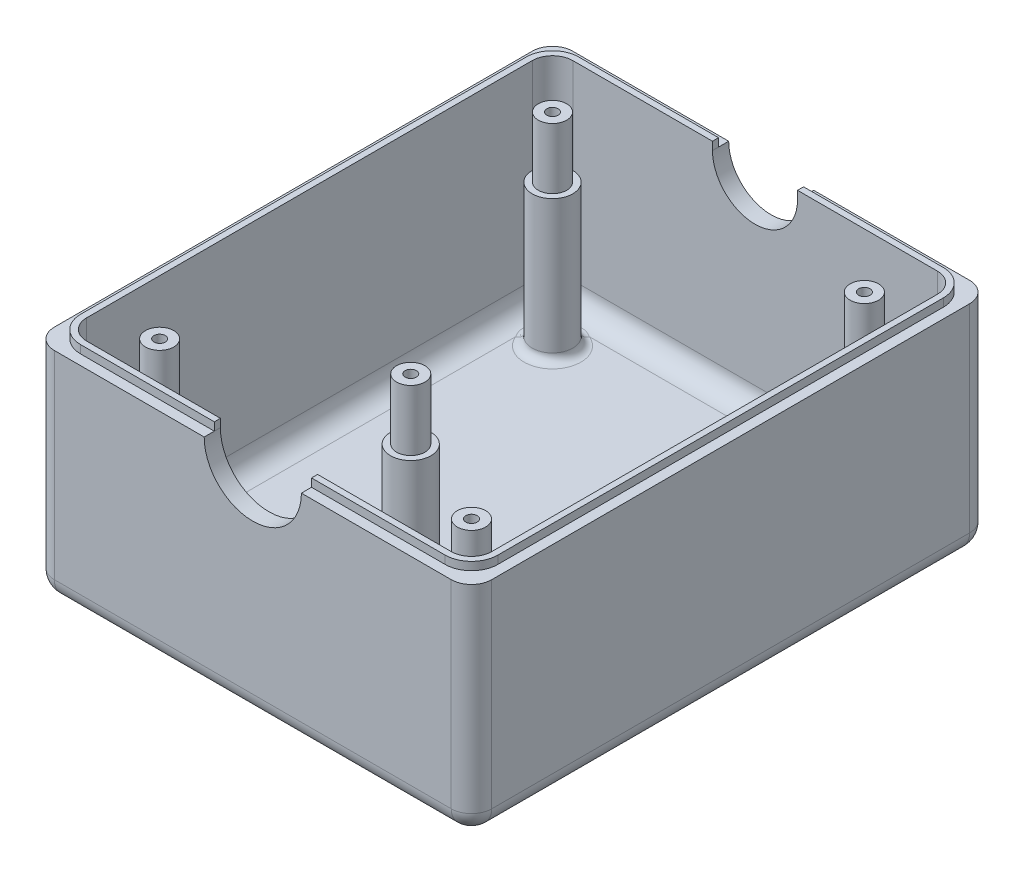
SolidWorks part; units mm, degrees
ref_plane "Front Plane" through (0, 0, 0) normal (0, 0, 1) x (1, 0, 0)
ref_plane "Top Plane" through (0, 0, 0) normal (0, 1, 0) x (1, 0, 0)
ref_plane "Right Plane" through (0, 0, 0) normal (1, 0, 0) x (0, 0, -1)
sketch "Sketch2" plane through (0, 0, 0) normal (0, 0, 1) x (1, 0, 0)
  line L0 (-50, 50) -> (-50, 0)
  line L1 (-50, 0) -> (50, 0)
  line L2 (50, 0) -> (50, 50)
  point P4 (0, 0)
  dimension "D1" = 50
  dimension "D2" = 100
  dimension "D3" = 50
extrude "Extrude-Thin2" add sketch "Sketch2" along normal blind 120 thin
sketch "Sketch5" plane through (0, 50, 0) normal (0, 1, 0) x (1, 0, 0)
  line L1 (-54, -120) -> (-50, -120) construction
  line L2 (-50, -120) -> (50, -120) construction
  line L3 (50, -120) -> (54, -120) construction
  line L4 (50, -120) -> (54, -120)
  line L5 (-50, -120) -> (50, -120)
  line L6 (-54, -120) -> (-50, -120)
extrude "Extrude-Thin3" add sketch "Sketch5" against normal up to surface (54 mm away) thin
sketch "Sketch7" plane through (0, 50, 0) normal (0, 1, 0) x (1, 0, 0)
  line L0 (50, 0) -> (54, 0) construction
  line L1 (-50, 0) -> (50, 0) construction
  line L2 (-54, 0) -> (-50, 0) construction
  line L3 (50, 0) -> (54, 0)
  line L4 (-50, 0) -> (50, 0)
  line L5 (-54, 0) -> (-50, 0)
extrude "Extrude-Thin4" add sketch "Sketch7" against normal up to surface (54 mm away) thin thin type one direction reverse wall 4
fillet "Fillet1" radius 5 7 edges at (54, -4, 60) (-54, -4, 60) (-54, 23, 124) (0, -4, 124) (54, 23, -4) (0, -4, -4) (-54, 23, -4)
fillet "Fillet2" radius 5 2 edges at (54, 25.5, 124) (52.5355, -2.5355, 122.5355)
fillet "Fillet3" radius 5 3 edges at (50, 0, 60) (0, 0, 0) (50, 25, 0)
fillet "Fillet4" radius 5 3 edges at (-50, 1.4645, 1.4645) (-50, 0, 62.5) (-50, 27.5, 0)
fillet "Fillet5" radius 5 5 edges at (50, 27.5, 120) (48.5355, 1.4645, 120) (0, 0, 120) (-48.5355, 1.4645, 120) (-50, 27.5, 120)
sketch "Sketch8" plane through (0, 0, 0) normal (0, 1, 0) x (1, 0, 0)
  line L0 (45, -5) -> (-45, -5) construction
  line L1 (-39.25, -15.7287) -> (39.25, -15.7287)
  line L2 (-39.25, -15.7287) -> (-39.25, -78.2287)
  line L3 (-39.25, -78.2287) -> (39.25, -78.2287)
  line L4 (39.25, -15.7287) -> (39.25, -78.2287)
  line L5 (45, -115) -> (45, -5) construction
  line L6 (0, 0) -> (0, -127.3693) construction
  line L7 (-45, -115) -> (45, -115) construction
  circle A0 centre (38.5, -11.5) radius 5
  circle A1 centre (-38.5, -11.5) radius 5
  circle A2 centre (-38.5, -108.5) radius 5
  circle A3 centre (38.5, -108.5) radius 5
  circle A4 centre (0, -85) radius 5
  point P4 (0, -15.7287)
  dimension "D7" = 10
  dimension "D8" = 10
  dimension "D9" = 10
  dimension "D1" = 78.5
  dimension "D2" = 62.5
  dimension "D3" = 6.5
  dimension "D4" = 6.5
  dimension "D5" = 6.5
  dimension "D6" = 30
extrude "Boss-Extrude1" add sketch "Sketch8" along normal blind 35 contours A1 | A0 | A4 | A2 | A3
sketch "Sketch10" plane through (0, 35, 0) normal (0, 1, 0) x (1, 0, 0)
  line L0 (0, 0) -> (0, -129.2583) construction
  circle A1 centre (38.5, -11.5) radius 5
  circle A2 centre (38.5, -11.5) radius 5
  circle A3 centre (38.5, -11.5) radius 3.5
  circle A4 centre (-38.5, -11.5) radius 3.5
  circle A5 centre (0, -85) radius 5 construction
  circle A6 centre (0, -85) radius 5
  circle A7 centre (0, -85) radius 3.5
  circle A8 centre (-38.5, -108.5) radius 5 construction
  circle A9 centre (-38.5, -108.5) radius 5
  circle A10 centre (-38.5, -108.5) radius 3.5
  circle A11 centre (38.5, -108.5) radius 3.5
  dimension "D2" = 7
  dimension "D3" = 7
  dimension "D4" = 7
  dimension "D1" = 0
extrude "Boss-Extrude2" add sketch "Sketch10" along normal up to surface (15 mm away) contours A3 | A4 | A7 | A11 | A10
sketch "Sketch11" plane through (0, 50, 0) normal (0, 1, 0) x (1, 0, 0)
  line L0 (0, 0) -> (0, -120) construction
  line L1 (45, -120) -> (-45, -120) construction
  circle A0 centre (-38.5, -11.5) radius 1.4
  circle A1 centre (-38.5, -11.5) radius 3.5
  circle A2 centre (-38.5, -11.5) radius 3.5
  circle A3 centre (38.5, -11.5) radius 1.4
  circle A4 centre (-38.5, -108.5) radius 1.4
  circle A5 centre (-38.5, -108.5) radius 3.5
  circle A6 centre (-38.5, -108.5) radius 3.5
  circle A7 centre (38.5, -108.5) radius 1.4
  circle A8 centre (0, -85) radius 1.4
  circle A9 centre (0, -85) radius 3.5
  circle A10 centre (0, -85) radius 3.5
  dimension "D2" = 2.8
  dimension "D4" = 2.8
  dimension "D6" = 2.8
  dimension "D1" = 0
  dimension "D3" = 0
  dimension "D5" = 0
extrude "Cut-Extrude1" cut sketch "Sketch11" against normal blind 28 contours A4 | A3 | A0 | A7 | A8
sketch "Sketch38" plane through (0, 0, 124) normal (0, 0, 1) x (1, 0, 0)
  line L0 (-49, 50) -> (49, 50) construction
  circle A0 centre (0, 50) radius 12
extrude "Cut-Extrude8" cut sketch "Sketch38" against normal blind 30
fillet "Fillet13" radius 2 1 edges at (-43.5, 0, 108.5)
sketch "Sketch40" plane through (0, 0, 0) normal (0, 1, 0) x (1, 0, 0)
  circle A0 centre (-38.5, -11.5) radius 3.75
  dimension "D1" = 7.5
extrude "Cut-Extrude9" cut sketch "Sketch40" against normal blind 32 and the other way blind 32
sketch "Sketch41" plane through (0, 0, 0) normal (0, 1, 0) x (1, 0, 0)
  circle A0 centre (38.5, -11.5) radius 3.75
  circle A1 centre (0, -85) radius 3.75
  circle A2 centre (-38.5, -108.5) radius 3.75
  circle A3 centre (38.5, -108.5) radius 3.75
  dimension "D1" = 7.5
  dimension "D2" = 7.5
  dimension "D3" = 7.5
  dimension "D4" = 7.5
extrude "Cut-Extrude10" cut sketch "Sketch41" along normal blind 32 and the other way blind 32
sketch "Sketch44" plane through (0, 50, 0) normal (0, 1, 0) x (1, 0, 0)
  line L0 (50, -5) -> (50, -115)
extrude "Extrude-Thin8" add sketch "Sketch44" along normal blind 2 thin thin type one direction reverse wall 1.5
sketch "Sketch50" plane through (0, 50, 0) normal (0, 1, 0) x (1, 0, 0)
  line L0 (-50, -5) -> (-50, -115)
extrude "Extrude-Thin12" add sketch "Sketch50" along normal blind 2 thin
sketch "Sketch51" plane through (0, 50, 0) normal (0, 1, 0) x (1, 0, 0)
  line L0 (-45, 0) -> (45, 0) construction
  line L1 (-45, 0) -> (45, 0) construction
  line L2 (-45, 0) -> (45, 0)
  line L3 (50, -5) -> (50, -115) construction
  line L4 (50, -5) -> (50, -115) construction
  arc A0 (-50, -5) -> (-45, 0) centre (-45, -5) cw
  arc A1 (45, 0) -> (50, -5) centre (45, -5) cw
extrude "Extrude-Thin13" add sketch "Sketch51" along normal blind 2 thin thin type one direction reverse wall 1.5
sketch "Sketch52" plane through (0, 50, 0) normal (0, 1, 0) x (1, 0, 0)
  line L0 (-45, -120) -> (-12, -120)
  arc A0 (-50, -115) -> (-45, -120) centre (-45, -115) ccw
  arc A1 (-50, -115) -> (-45, -120) centre (-45, -115) ccw construction
  arc A2 (-50, -115) -> (-45, -120) centre (-45, -115) ccw construction
extrude "Extrude-Thin14" add sketch "Sketch52" along normal blind 2 thin
sketch "Sketch53" plane through (0, 50, 0) normal (0, 1, 0) x (1, 0, 0)
  line L0 (45, -120) -> (12, -120)
  arc A0 (50, -115) -> (45, -120) centre (45, -115) cw
extrude "Extrude-Thin15" add sketch "Sketch53" along normal blind 2 thin thin type one direction reverse wall 1.5
sketch "Sketch60" plane through (0, 0, -4) normal (0, 0, -1) x (-1, 0, 0)
  line L0 (49, 50) -> (-49, 50) construction
  circle A0 centre (0, 50) radius 10.5
  dimension "D1" = 21
extrude "Cut-Extrude13" cut sketch "Sketch60" against normal blind 10
sketch "Sketch61" plane through (0, 0, -4) normal (0, 0, -1) x (-1, 0, 0)
  line L1 (-10.5, 50) -> (10.5, 50)
  line L2 (-10.5, 50) -> (-10.5, 52.7523)
  line L3 (-10.5, 52.7523) -> (10.5, 52.7523)
  line L4 (10.5, 50) -> (10.5, 52.7523)
extrude "Cut-Extrude14" cut sketch "Sketch61" against normal blind 10
fillet "Fillet14" radius 2 4 edges at (-43.5, 0, 11.5) (33.5, 0, 11.5) (-5, 0, 85) (33.5, 0, 108.5)
sketch "Sketch65" plane through (0, 32, 0) normal (0, -1, 0) x (1, 0, 0)
  line L0 (0, 0) -> (0, 117.6476) construction
  circle A0 centre (38.5, 108.5) radius 3.75 construction
  circle A1 centre (-38.5, 108.5) radius 3.75 construction
  circle A2 centre (0, 85) radius 3.75 construction
  circle A3 centre (38.5, 11.5) radius 3.75 construction
  circle A4 centre (-38.5, 11.5) radius 3.75 construction
  circle A5 centre (38.5, 108.5) radius 3.75
  circle A6 centre (-38.5, 108.5) radius 3.75
  circle A7 centre (0, 85) radius 3.75
  circle A8 centre (38.5, 11.5) radius 3.75
  circle A9 centre (-38.5, 11.5) radius 3.75
  circle A10 centre (-38.5, 108.5) radius 1.75
  circle A11 centre (38.5, 108.5) radius 1.75
  circle A13 centre (0, 85) radius 1.75
  circle A14 centre (-38.5, 11.5) radius 1.75
  circle A15 centre (38.5, 11.5) radius 1.75
  dimension "D1" = 3.5
  dimension "D2" = 3.5
  dimension "D3" = 3.5
extrude "Cut-Extrude17" cut sketch "Sketch65" against normal blind 10 contours A10 | A14 | A15 | A11 | A13
